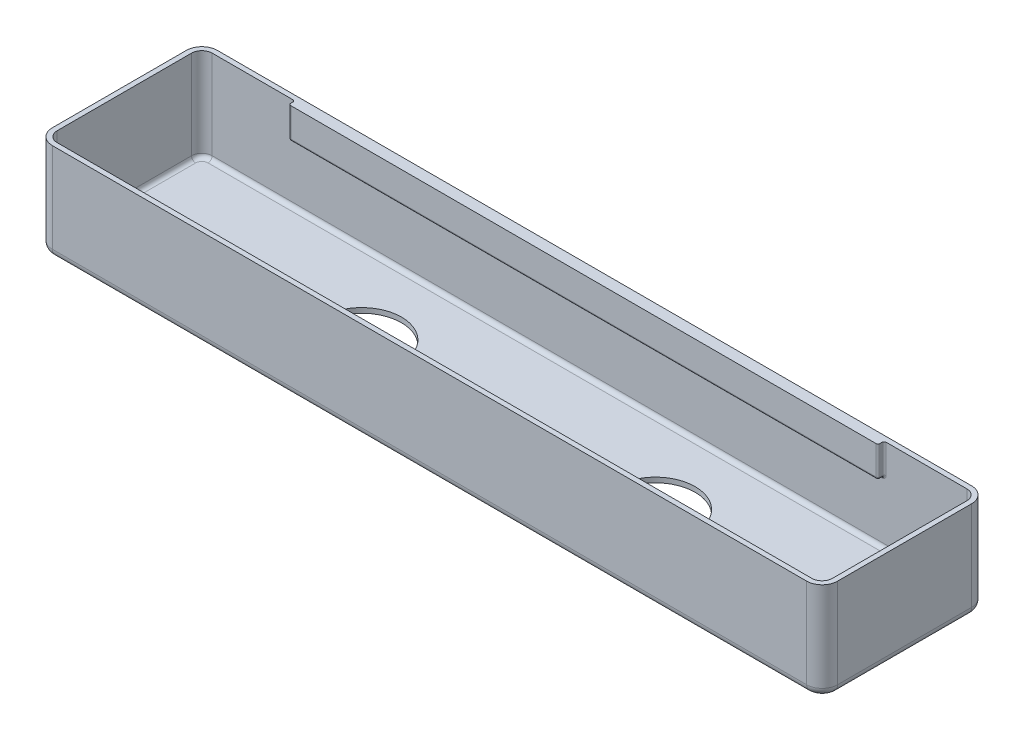
SolidWorks part; units mm, degrees
material "NEOPRENE"
ref_plane "Front" through (0, 0, 0) normal (0, 0, 1) x (1, 0, 0)
ref_plane "Top" through (0, 0, 0) normal (0, 1, 0) x (1, 0, 0)
ref_plane "Right" through (0, 0, 0) normal (1, 0, 0) x (0, 0, -1)
sketch "Sketch1" plane through (0, 0, 0) normal (0, 1, 0) x (1, 0, 0)
  line L0 (-119.0625, 0) -> (-120.5865, 0) construction
  line L1 (-120.5865, 25.3365) -> (120.5865, 25.3365)
  line L2 (-120.5865, 25.3365) -> (-120.5865, -25.3365)
  line L3 (-120.5865, -25.3365) -> (120.5865, -25.3365)
  line L4 (120.5865, 25.3365) -> (120.5865, -25.3365)
  line L5 (-120.5865, 25.3365) -> (120.5865, -25.3365) construction
  line L6 (-120.5865, -25.3365) -> (120.5865, 25.3365) construction
  line L7 (119.0625, 23.8125) -> (-119.0625, 23.8125)
  line L8 (119.0625, 23.8125) -> (119.0625, -23.8125)
  line L9 (119.0625, -23.8125) -> (-119.0625, -23.8125)
  line L10 (-119.0625, 23.8125) -> (-119.0625, -23.8125)
  line L11 (119.0625, 23.8125) -> (-119.0625, -23.8125) construction
  line L12 (119.0625, -23.8125) -> (-119.0625, 23.8125) construction
  line L13 (0, 23.8125) -> (0, 25.3365) construction
  point P0 (0, 0)
  point P6 (0, 0)
  dimension "D1" = 238.125
  dimension "D2" = 47.625
  dimension "THICKNESS" = 1.524
extrude "Boss-Extrude1" add sketch "Sketch1" along normal blind 38.1
sketch "Sketch2" plane through (0, 0, 0) normal (0, -1, 0) x (1, 0, 0)
  line L4 (120.5865, -25.3365) -> (120.5865, 25.3365)
  line L5 (120.5865, 25.3365) -> (-120.5865, 25.3365)
  line L6 (-120.5865, 25.3365) -> (-120.5865, -25.3365)
  line L7 (-120.5865, -25.3365) -> (120.5865, -25.3365)
  line L8 (120.5865, -25.3365) -> (120.5865, 25.3365)
  line L9 (120.5865, 25.3365) -> (-120.5865, 25.3365)
  line L10 (-120.5865, 25.3365) -> (-120.5865, -25.3365)
  line L11 (-120.5865, -25.3365) -> (120.5865, -25.3365)
  arc A0 (104.4707, 2.6288) -> (104.0355, 6.8062) centre (104.2531, 4.7175) ccw construction
  arc A1 (104.0355, 6.8062) -> (104.4707, 2.6288) centre (104.2531, 4.7175) ccw construction
  arc A2 (73.6375, -0.5832) -> (73.2023, 3.5942) centre (73.4199, 1.5055) ccw construction
  arc A3 (73.2023, 3.5942) -> (73.6375, -0.5832) centre (73.4199, 1.5055) ccw construction
  arc A4 (104.4707, 2.6288) -> (104.0355, 6.8062) centre (104.2531, 4.7175) ccw
  arc A5 (104.0355, 6.8062) -> (104.4707, 2.6288) centre (104.2531, 4.7175) ccw
  arc A6 (73.6375, -0.5832) -> (73.2023, 3.5942) centre (73.4199, 1.5055) ccw
  arc A7 (73.2023, 3.5942) -> (73.6375, -0.5832) centre (73.4199, 1.5055) ccw
  dimension "D1" = 0
extrude "Boss-Extrude2" add sketch "Sketch2" along normal blind 1.524
fillet "Fillet1" radius 3.175 4 edges at (119.0625, 19.05, -23.8125) (119.0625, 19.05, 23.8125) (-119.0625, 19.05, 23.8125) (-119.0625, 19.05, -23.8125)
fillet "Fillet2" radius 4.7625 4 edges at (-120.5865, 18.288, -25.3365) (120.5865, 18.288, -25.3365) (120.5865, 18.288, 25.3365) (-120.5865, 18.288, 25.3365)
sketch "Sketch4" plane through (0, -1.524, 0) normal (0, -1, 0) x (1, 0, 0)
  line L2 (120.5865, -20.574) -> (120.5865, 20.574) construction
  line L3 (115.824, 25.3365) -> (-115.824, 25.3365) construction
  circle A0 centre (88.8365, 3.1115) radius 12.065
  dimension "D1" = 24.13
  dimension "D3" = 22.225
  dimension "D2" = 31.75
extrude "Cut-Extrude2" [suppressed] cut sketch "Sketch4" against normal through all
sketch "Sketch5" plane through (0, 0, -23.8125) normal (0, 0, 1) x (1, 0, 0)
  line L0 (0, 0) -> (0, 28.575) construction
  line L1 (115.8875, 38.1) -> (-115.8875, 38.1) construction
  line L2 (-90.4875, 19.05) -> (90.4875, 19.05)
  line L3 (-90.4875, 19.05) -> (-90.4875, 38.1)
  line L4 (-90.4875, 38.1) -> (90.4875, 38.1)
  line L5 (90.4875, 19.05) -> (90.4875, 38.1)
  line L6 (-90.4875, 19.05) -> (90.4875, 38.1) construction
  line L7 (-90.4875, 38.1) -> (90.4875, 19.05) construction
  dimension "D1" = 180.975
  dimension "D2" = 19.05
extrude "Boss-Extrude3" add sketch "Sketch5" along normal blind 1.905
fillet "Fillet3" radius 0.635 8 edges at (0, 19.05, -21.9075) (0, 19.05, -23.8125) (-90.4875, 28.575, -23.8125) (-90.4875, 28.575, -21.9075) (90.4875, 28.575, -21.9075) (90.4875, 28.575, -23.8125) (-90.4875, 19.05, -22.86) (90.4875, 19.05, -22.86)
fillet "Fillet4" radius 1.27 8 edges at (118.1326, 0, -22.8826) (119.0625, 0, 0) (118.1326, 0, 22.8826) (0, 0, 23.8125) (-118.1326, 0, 22.8826) (-119.0625, 0, 0) (-118.1326, 0, -22.8826) (0, 0, -23.8125)
fillet "Fillet5" radius 2.54 8 edges at (-119.1916, -1.524, 23.9416) (0, -1.524, 25.3365) (119.1916, -1.524, 23.9416) (120.5865, -1.524, 0) (119.1916, -1.524, -23.9416) (0, -1.524, -25.3365) (-119.1916, -1.524, -23.9416) (-120.5865, -1.524, 0)
sketch "Sketch6" plane through (0, -1.524, 0) normal (0, -1, 0) x (1, 0, 0)
  circle A0 centre (73.4199, 1.5055) radius 2.1 construction
  circle A1 centre (73.4199, 1.5055) radius 2.1
  circle A2 centre (104.2531, 4.7175) radius 2.1 construction
  circle A3 centre (104.2531, 4.7175) radius 2.1
extrude "Boss-Extrude4" add sketch "Sketch6" against normal up to surface (1.524 mm away) up to face at (0, 0, 0)
sketch "Sketch7" plane through (0, -1.524, 0) normal (0, -1, 0) x (1, 0, 0)
  circle A0 centre (-45.2, 0.936) radius 12.192
  circle A1 centre (45, 0.936) radius 12.192
  dimension "D1" = 24.384
extrude "Cut-Extrude3" cut sketch "Sketch7" against normal through all
sketch "Sketch8" plane through (0, 38.1, 0) normal (0, 1, 0) x (1, 0, 0)
  line L0 (-90.4875, 22.5425) -> (-90.4875, 23.1775) construction
  line L1 (89.8525, 21.9075) -> (-89.8525, 21.9075) construction
  line L2 (90.4875, 22.5425) -> (90.4875, 23.1775) construction
  line L3 (115.8875, 23.8125) -> (91.1225, 23.8125) construction
  line L4 (115.824, 25.3365) -> (-115.824, 25.3365)
  line L5 (-120.5865, 20.574) -> (-120.5865, -20.574)
  line L6 (-115.824, -25.3365) -> (115.824, -25.3365)
  line L7 (120.5865, -20.574) -> (120.5865, 20.574)
  line L8 (115.824, 25.3365) -> (-115.824, 25.3365)
  line L9 (-120.5865, 20.574) -> (-120.5865, -20.574)
  line L10 (-115.824, -25.3365) -> (115.824, -25.3365)
  line L11 (120.5865, -20.574) -> (120.5865, 20.574)
  line L12 (119.0625, -20.6375) -> (119.0625, 20.6375) construction
  line L13 (-115.8875, -23.8125) -> (115.8875, -23.8125) construction
  line L14 (-91.1225, 23.8125) -> (-115.8875, 23.8125) construction
  line L15 (-119.0625, 20.6375) -> (-119.0625, -20.6375) construction
  line L16 (-90.4875, 22.5425) -> (-90.4875, 23.1775)
  line L17 (89.8525, 21.9075) -> (-89.8525, 21.9075)
  line L18 (90.4875, 22.5425) -> (90.4875, 23.1775)
  line L19 (115.8875, 23.8125) -> (91.1225, 23.8125)
  line L20 (119.0625, -20.6375) -> (119.0625, 20.6375)
  line L21 (-115.8875, -23.8125) -> (115.8875, -23.8125)
  line L22 (-91.1225, 23.8125) -> (-115.8875, 23.8125)
  line L23 (-119.0625, 20.6375) -> (-119.0625, -20.6375)
  arc A0 (-90.4875, 23.1775) -> (-91.1225, 23.8125) centre (-91.1225, 23.1775) ccw construction
  arc A1 (-90.4875, 22.5425) -> (-89.8525, 21.9075) centre (-89.8525, 22.5425) ccw construction
  arc A2 (89.8525, 21.9075) -> (90.4875, 22.5425) centre (89.8525, 22.5425) ccw construction
  arc A3 (91.1225, 23.8125) -> (90.4875, 23.1775) centre (91.1225, 23.1775) ccw construction
  arc A4 (-115.824, 25.3365) -> (-120.5865, 20.574) centre (-115.824, 20.574) ccw
  arc A5 (-120.5865, -20.574) -> (-115.824, -25.3365) centre (-115.824, -20.574) ccw
  arc A6 (115.824, -25.3365) -> (120.5865, -20.574) centre (115.824, -20.574) ccw
  arc A7 (120.5865, 20.574) -> (115.824, 25.3365) centre (115.824, 20.574) ccw
  arc A8 (-115.824, 25.3365) -> (-120.5865, 20.574) centre (-115.824, 20.574) ccw
  arc A9 (-120.5865, -20.574) -> (-115.824, -25.3365) centre (-115.824, -20.574) ccw
  arc A10 (115.824, -25.3365) -> (120.5865, -20.574) centre (115.824, -20.574) ccw
  arc A11 (120.5865, 20.574) -> (115.824, 25.3365) centre (115.824, 20.574) ccw
  arc A12 (119.0625, 20.6375) -> (115.8875, 23.8125) centre (115.8875, 20.6375) ccw construction
  arc A13 (115.8875, -23.8125) -> (119.0625, -20.6375) centre (115.8875, -20.6375) ccw construction
  arc A14 (-115.8875, 23.8125) -> (-119.0625, 20.6375) centre (-115.8875, 20.6375) ccw construction
  arc A15 (-119.0625, -20.6375) -> (-115.8875, -23.8125) centre (-115.8875, -20.6375) ccw construction
  arc A16 (-90.4875, 23.1775) -> (-91.1225, 23.8125) centre (-91.1225, 23.1775) ccw
  arc A17 (-90.4875, 22.5425) -> (-89.8525, 21.9075) centre (-89.8525, 22.5425) ccw
  arc A18 (89.8525, 21.9075) -> (90.4875, 22.5425) centre (89.8525, 22.5425) ccw
  arc A19 (91.1225, 23.8125) -> (90.4875, 23.1775) centre (91.1225, 23.1775) ccw
  arc A20 (119.0625, 20.6375) -> (115.8875, 23.8125) centre (115.8875, 20.6375) ccw
  arc A21 (115.8875, -23.8125) -> (119.0625, -20.6375) centre (115.8875, -20.6375) ccw
  arc A22 (-115.8875, 23.8125) -> (-119.0625, 20.6375) centre (-115.8875, 20.6375) ccw
  arc A23 (-119.0625, -20.6375) -> (-115.8875, -23.8125) centre (-115.8875, -20.6375) ccw
  dimension "D1" = 0
extrude "Cut-Extrude4" cut sketch "Sketch8" against normal blind 9.525
equation "\"D1@Boss-Extrude2\"=\"THICKNESS\""
